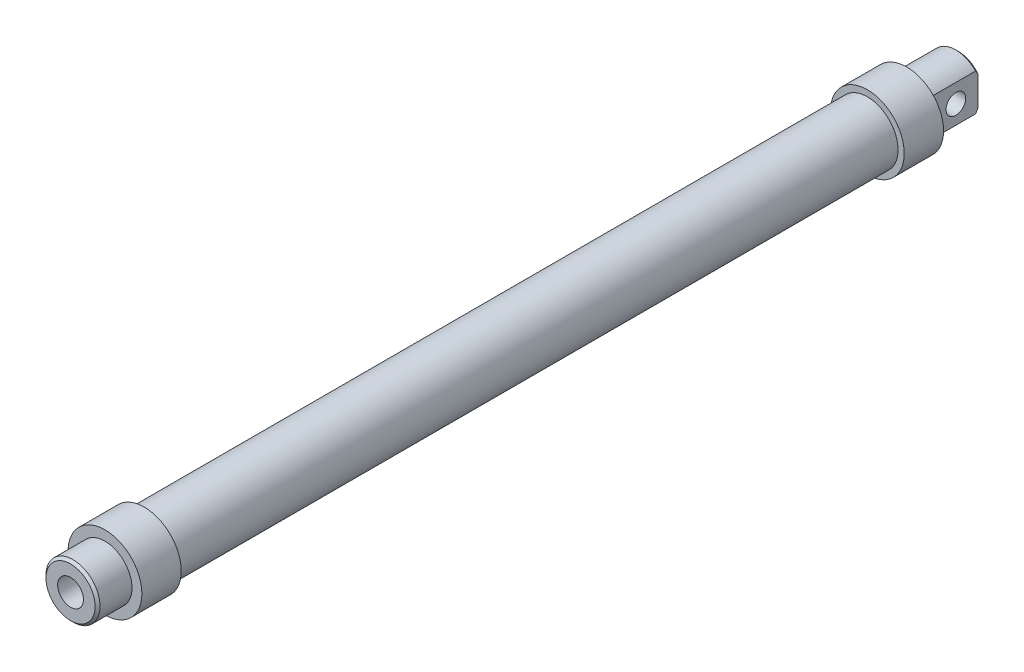
SolidWorks part; units mm, degrees
ref_plane "Plan de face" through (0, 0, 0) normal (0, 0, 1) x (1, 0, 0)
ref_plane "Plan de dessus" through (0, 0, 0) normal (0, 1, 0) x (1, 0, 0)
ref_plane "Plan de droite" through (0, 0, 0) normal (1, 0, 0) x (0, 0, -1)
sketch "Esquisse1" plane through (0, 0, 0) normal (0, 0, 1) x (1, 0, 0)
  circle A0 centre (0, 0) radius 12.5
  dimension "D1" = 25
extrude "Boss.-Extru.1" add sketch "Esquisse1" along normal blind 326
sketch "Esquisse2" plane through (0, 0, 326) normal (0, 0, 1) x (1, 0, 0)
  circle A0 centre (0, 0) radius 15
  dimension "D1" = 30
extrude "Boss.-Extru.2" add sketch "Esquisse2" against normal blind 16
extrude "Boss.-Extru.4" add sketch "Esquisse2<2>" along normal blind 16 from offset 326 offset against normal yes
sketch "Esquisse2<2>" plane through (0, 0, 326) normal (0, 0, 1) x (1, 0, 0) same geometry as "Esquisse2"
sketch "Esquisse3" plane through (0, 0, 0) normal (0, 0, -1) x (-1, 0, 0)
  circle A0 centre (0, 0) radius 11
  dimension "D1" = 22
extrude "Boss.-Extru.5" add sketch "Esquisse3" along normal blind 21
sketch "Esquisse4" plane through (0, 0, -21) normal (0, 0, -1) x (-1, 0, 0)
  line L0 (0, -11) -> (0, 11) construction
  line L1 (-8, -11) -> (0, -11) construction
  line L2 (-8, 11) -> (-13, 11)
  line L3 (-8, 11) -> (-8, -11)
  line L4 (-8, -11) -> (-13, -11)
  line L5 (-13, 11) -> (-13, -11)
  line L6 (-8, 11) -> (0, 11) construction
  line L7 (13, 11) -> (13, -11)
  line L8 (8, -11) -> (13, -11)
  line L9 (8, 11) -> (8, -11)
  line L10 (8, 11) -> (13, 11)
  circle A0 centre (0, 0) radius 11 construction
  circle A1 centre (0, 0) radius 11 construction
  dimension "D1" = 16
  dimension "D2" = 5
extrude "Enlèv. mat.-Extru.1" cut sketch "Esquisse4" against normal blind 19
sketch "Esquisse5" plane through (8, 0, 0) normal (1, 0, 0) x (0, 0, -1)
  line L0 (12, 0) -> (21, 0) construction
  line L1 (21, -7.5498) -> (21, 7.5498) construction
  line L2 (0, -15) -> (0, 15) construction
  circle A0 centre (12, 0) radius 4
  dimension "D2" = 8
  dimension "D1" = 12
extrude "Enlèv. mat.-Extru.2" cut sketch "Esquisse5" against normal through all
sketch "Esquisse6" plane through (0, 0, 326) normal (0, 0, 1) x (1, 0, 0)
  circle A0 centre (0, 0) radius 11
  dimension "D1" = 22
extrude "Boss.-Extru.6" add sketch "Esquisse6" along normal blind 14
chamfer "Chanfrein1" distance 1 angle 45 5 edges at (-8, 0, -2) (8, 0, -2) (0, -11, -21) (0, 11, -21) (11, 0, 340)
sketch "Esquisse7" plane through (0, 0, 340) normal (0, 0, 1) x (1, 0, 0)
  circle A0 centre (0, 0) radius 5.25
  dimension "D1" = 10.5
extrude "Enlèv. mat.-Extru.3" cut sketch "Esquisse7" against normal blind 250
